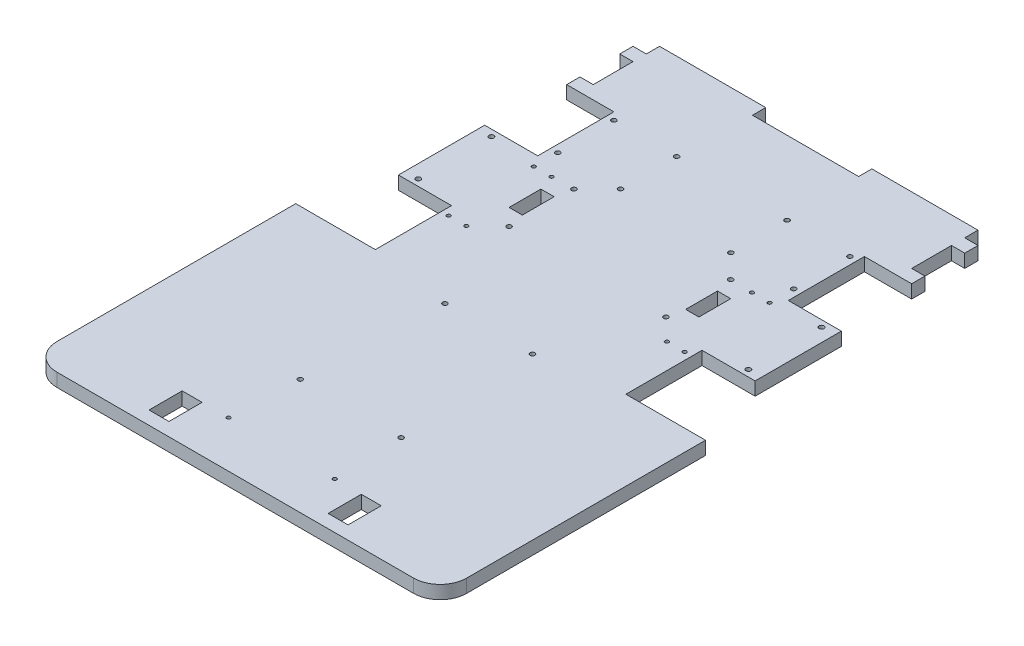
SolidWorks part; units mm, degrees
ref_plane "Front Plane" through (0, 0, 0) normal (0, 0, 1) x (1, 0, 0)
ref_plane "Top Plane" through (0, 0, 0) normal (0, 1, 0) x (1, 0, 0)
ref_plane "Right Plane" through (0, 0, 0) normal (1, 0, 0) x (0, 0, -1)
sketch "Sketch1" plane through (0, 0, 0) normal (0, 1, 0) x (1, 0, 0)
  line L0 (-147.6422, 18.3147) -> (-147.6422, -22.9603)
  line L1 (-138.4922, 92.8637) -> (-87.6922, 92.8637)
  line L2 (-122.2422, 54.7637) -> (-144.8422, 54.7637)
  line L3 (-62.2922, 86.5137) -> (-62.2922, -186.4093)
  line L4 (-62.2922, -186.4093) -> (-147.6422, -186.4093)
  line L5 (-144.8422, 54.7637) -> (-144.8422, 61.1137)
  line L6 (-144.8422, 80.1637) -> (-144.8422, 86.5137)
  line L7 (-147.6422, 18.3147) -> (-122.2422, 18.3147)
  line L8 (-122.2422, 54.7637) -> (-122.2422, 18.3147)
  line L9 (-147.6422, -22.9603) -> (-122.2422, -22.9603)
  line L10 (-107.7247, -9.9428) -> (-101.3747, -9.9428)
  line L11 (-160.3422, -173.7093) -> (-160.3422, -72.1093)
  line L12 (-122.2422, -22.9603) -> (-122.2422, -59.4093)
  line L13 (-147.6422, -59.4093) -> (-122.2422, -59.4093)
  line L14 (-107.7247, -9.9428) -> (-107.7247, 5.2972)
  line L15 (-107.7247, 5.2972) -> (-101.3747, 5.2972)
  line L16 (-101.3747, -9.9428) -> (-101.3747, 5.2972)
  line L17 (-107.7247, -9.9428) -> (-101.3747, 5.2972) construction
  line L18 (-107.7247, 5.2972) -> (-101.3747, -9.9428) construction
  line L19 (-160.3422, -72.1093) -> (-160.3422, -59.4093)
  line L20 (-160.3422, -59.4093) -> (-147.6422, -59.4093)
  line L21 (-144.8422, 86.5137) -> (-138.4922, 86.5137)
  line L22 (-138.4922, 92.8637) -> (-138.4922, 86.5137)
  line L23 (-144.8422, 80.1637) -> (-138.4922, 80.1637)
  line L25 (-144.8422, 61.1137) -> (-138.4922, 61.1137)
  line L26 (-138.4922, 80.1637) -> (-138.4922, 61.1137)
  line L27 (-62.2922, 86.5137) -> (-87.6922, 86.5137)
  line L28 (-87.6922, 92.8637) -> (-87.6922, 86.5137)
  line L29 (-100.3922, -164.1843) -> (-109.9172, -164.1843)
  line L30 (-100.3922, -164.1843) -> (-100.3922, -180.0593)
  line L31 (-100.3922, -180.0593) -> (-109.9172, -180.0593)
  line L32 (-109.9172, -164.1843) -> (-109.9172, -180.0593)
  circle A0 centre (-118.7497, -27.8153) radius 0.889
  circle A1 centre (-118.7497, 12.9197) radius 0.889
  circle A2 centre (-110.2647, 12.9197) radius 0.889
  circle A3 centre (-110.2647, -27.8153) radius 0.889
  circle A4 centre (-118.7497, 51.2712) radius 1.1303
  circle A5 centre (-118.7497, 24.398) radius 1.1303
  circle A6 centre (-88.7015, 51.2712) radius 1.1303
  circle A7 centre (-88.7015, 24.398) radius 1.1303
  circle A8 centre (-99.7922, 13.1772) radius 1.1303
  circle A9 centre (-99.7922, -17.8228) radius 1.1303
  circle A10 centre (-83.2472, -65.1243) radius 1.1303
  circle A11 centre (-86.4222, -131.1643) radius 1.1303
  arc A12 (-147.6422, -186.4093) -> (-160.3422, -173.7093) centre (-147.6422, -173.7093) cw
  circle A13 centre (-87.6922, -164.1843) radius 0.889
  point P14 (-104.5497, -2.3228)
  point P49 (-160.3422, -186.4093)
  point P52 (-160.3422, -59.4093)
  dimension "D9" = 1.778
  dimension "D10" = 1.778
  dimension "D11" = 3.4925
  dimension "D12" = 3.4925
  dimension "D14" = 4.855
  dimension "D21" = 3.4925
  dimension "D22" = 3.4925
  dimension "D23" = 26.8732
  dimension "D24" = 30.0482
  dimension "D25" = 2.2606
  dimension "D26" = 2.2606
  dimension "D27" = 2.2606
  dimension "D28" = 2.2606
  dimension "D35" = 2.2606
  dimension "D36" = 2.2606
  dimension "D37" = 31
  dimension "D38" = 15.5
  dimension "D39" = 37.5
  dimension "D41" = 2.2606
  dimension "D42" = 20.955
  dimension "D43" = 2.2606
  dimension "D44" = 66.04
  dimension "D45" = 24.13
  dimension "D46" = 12.7
  dimension "D52" = 22.225
  dimension "D53" = 25.4
  dimension "D54" = 1.778
  dimension "D1" = 41.275
  dimension "D2" = 25.4
  dimension "D3" = 25.4
  dimension "D4" = 36.449
  dimension "D5" = 36.449
  dimension "D6" = 22.6
  dimension "D7" = 38.1
  dimension "D8" = 9.525
  dimension "D13" = 5.395
  dimension "D16" = 2.54
  dimension "D17" = 15.24
  dimension "D18" = 20.6375
  dimension "D19" = 6.35
  dimension "D20" = 127
  dimension "D29" = 6.35
  dimension "D30" = 6.35
  dimension "D31" = 6.35
  dimension "D32" = 6.35
  dimension "D33" = 6.35
  dimension "D34" = 0
  dimension "D40" = 5.715
  dimension "D47" = 6.35
  dimension "D48" = 25.4
  dimension "D49" = 15.875
  dimension "D50" = 6.35
  dimension "D51" = 38.1
  dimension "D55" = 50.8
  dimension "D15" = 2
extrude "Boss-Extrude1" add sketch "Sketch1" along normal blind 6.35
sketch "Sketch2" plane through (0, 6.35, 0) normal (0, 1, 0) x (1, 0, 0)
  line L0 (-147.6422, 18.3147) -> (-147.6422, -22.9603) construction
  circle A0 centre (-141.2922, 15.1772) radius 1.1684
  circle A1 centre (-141.2922, -19.8228) radius 1.1684
  point P6 (-147.6422, -2.3228)
  point P7 (-147.6422, -2.3228)
  dimension "D1" = 2.3368
  dimension "D2" = 2.3368
  dimension "D3" = 6.35
  dimension "D4" = 6.35
  dimension "D5" = 17.5
  dimension "D6" = 17.5
extrude "Cut-Extrude1" cut sketch "Sketch2" against normal blind 6.35
mirror "Mirror1" about plane through (-62.2922, 6.35, -86.5137) normal (-1, 0, 0) of "Cut-Extrude1", "Boss-Extrude1"
